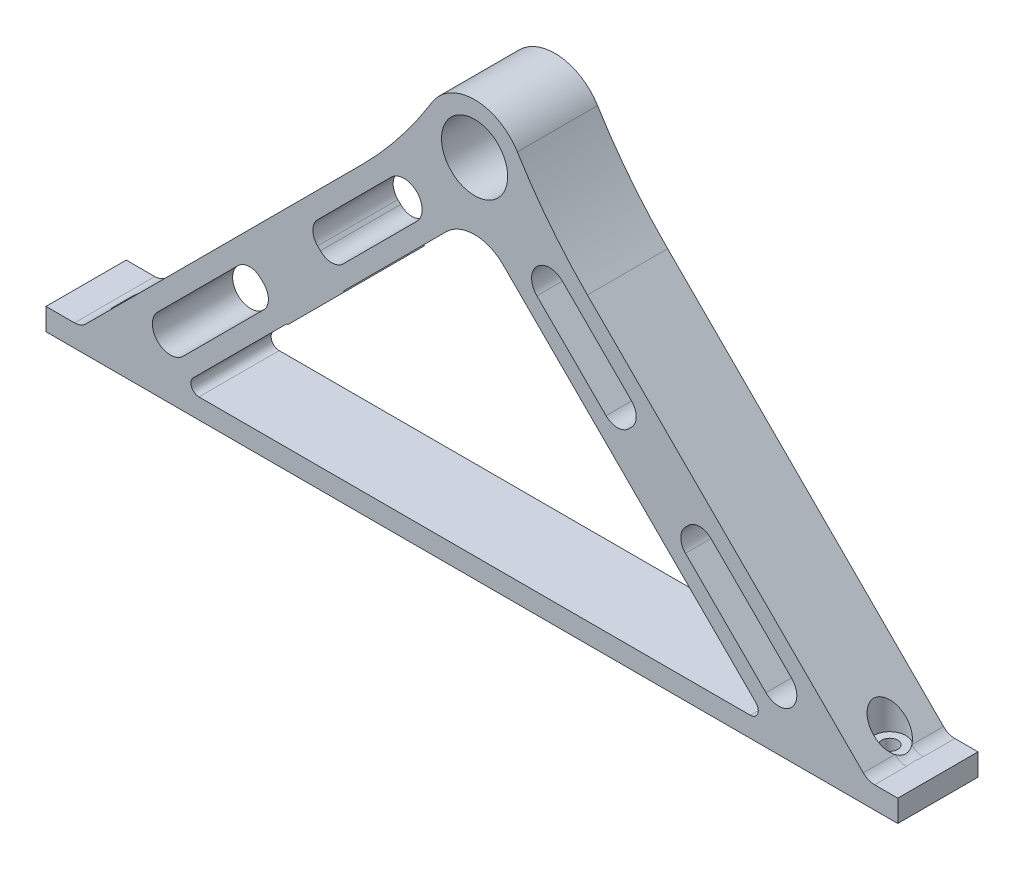
SolidWorks part; units mm, degrees
ref_plane "Ön Düzlem" through (0, 0, 0) normal (0, 0, 1) x (1, 0, 0)
ref_plane "Üst Düzlem" through (0, 0, 0) normal (0, 1, 0) x (1, 0, 0)
ref_plane "Sağ Düzlem" through (0, 0, 0) normal (1, 0, 0) x (0, 0, -1)
sketch "Çizim1" plane through (0, 0, 0) normal (0, 0, 1) x (1, 0, 0)
  line L1 (0, -12.5) -> (-73.5391, -86.0391)
  line L2 (-12.5, 0) -> (-98.0599, -85.5599)
  line L5 (0, -12.5) -> (73.5391, -86.0391)
  line L6 (12.5, 0) -> (98.0599, -85.5599)
  line L8 (-106.828, -91.0391) -> (-81.828, -91.0391)
  line L9 (105.4805, -91.0391) -> (80.4805, -91.0391)
  line L11 (-106.828, -91.0391) -> (-73.5391, -91.0391)
  line L12 (-106.828, -91.0391) -> (-106.828, -85.5599)
  line L13 (-106.828, -85.5599) -> (-98.0599, -85.5599)
  line L14 (-73.5391, -91.0391) -> (-73.5391, -86.0391)
  line L15 (105.4805, -91.0391) -> (73.5391, -91.0391)
  line L16 (105.4805, -91.0391) -> (105.4805, -85.5599)
  line L17 (105.4805, -85.5599) -> (98.0599, -85.5599)
  line L18 (73.5391, -91.0391) -> (73.5391, -86.0391)
  circle A0 centre (0, 0) radius 8.25
  arc A1 (12.5, 0) -> (-12.5, 0) centre (0, 0) ccw
  point P18 (0, 0)
  point P19 (0, 0)
  dimension "D1" = 16.5
  dimension "D2" = 25
  dimension "D3" = 5
  dimension "D4" = 5
  dimension "D5" = 104
  dimension "D6" = 104
  dimension "D7" = 121
  dimension "D8" = 121
extrude "Yükseklik-Ekstrüzyon1" add sketch "Çizim1" along normal blind 20 contours L6 A1 L2 L13 L12 L8 L11 L14 L1 L5 L18 L15 L9 L16 L17 A0 region at (-38.4398, -47.5993, 0)
sketch "Çizim2" plane through (0, -91.0391, 0) normal (0, -1, 0) x (-1, 0, 0)
  line L1 (-105.4805, -20) -> (-73.5391, -20) construction
  line L2 (-105.4805, -20) -> (-105.4805, 0) construction
  line L3 (106.828, -20) -> (106.828, 0) construction
  circle A0 centre (-93.4805, -10) radius 4
  circle A1 centre (94.828, -10) radius 4
  dimension "D2" = 8
  dimension "D5" = 8
  dimension "D1" = 10
  dimension "D3" = 12
  dimension "D4" = 12
extrude "Kes-Ekstrüzyon1" cut sketch "Çizim2" against normal blind 20 from offset 6 offset against normal yes
sketch "Çizim3" plane through (0, -85.0391, 0) normal (0, 1, 0) x (1, 0, 0)
  circle A0 centre (93.4805, -10) radius 2
  circle A1 centre (-94.828, -10) radius 2
  dimension "D1" = 4
  dimension "D2" = 4
extrude "Kes-Ekstrüzyon2" cut sketch "Çizim3" against normal blind 20
fillet "Radyus2" radius 120 2 edges at (-12.5, 0, 10) (12.5, 0, 10)
fillet "Radyus4" radius 10 1 edges at (0, -12.5, 10)
sketch "Çizim4" plane through (0, 0, 0) normal (0, 0, -1) x (-1, 0, 0)
  line L0 (-75.8112, -76.0391) -> (-18.7089, -18.9368) construction
  line L1 (-78.9932, -72.8571) -> (-21.8909, -15.7548)
  line L2 (-72.6292, -79.2211) -> (-15.5269, -22.1188)
  line L3 (17.5832, -17.8111) -> (75.8112, -76.0391) construction
  line L4 (20.7651, -14.6291) -> (78.9932, -72.8571)
  line L5 (14.4012, -20.9931) -> (72.6292, -79.2211)
  line L7 (-105.4805, -91.0391) -> (-73.5391, -91.0391) construction
  line L8 (-28.1224, -15.6224) -> (-98.0599, -85.5599) construction
  line L14 (106.828, -91.0391) -> (73.5391, -91.0391) construction
  line L15 (28.1224, -15.6224) -> (98.0599, -85.5599) construction
  arc A0 (-78.9932, -72.8571) -> (-72.6292, -79.2211) centre (-75.8112, -76.0391) ccw
  arc A1 (-15.5269, -22.1188) -> (-21.8909, -15.7548) centre (-18.7089, -18.9368) ccw
  arc A2 (20.7651, -14.6291) -> (14.4012, -20.9931) centre (17.5832, -17.8111) ccw
  arc A3 (72.6292, -79.2211) -> (78.9932, -72.8571) centre (75.8112, -76.0391) ccw
  point P2 (-47.26, -47.488)
  point P7 (46.6972, -46.9251)
  dimension "D4" = 4.5
  dimension "D5" = 4.5
  dimension "D1" = 15
  dimension "D2" = 9
  dimension "D3" = 9
  dimension "D6" = 15
  dimension "D7" = 9
  dimension "D8" = 9
extrude "Kes-Ekstrüzyon3" cut sketch "Çizim4" against normal blind 20
sketch "Çizim5" plane through (0, 0, 0) normal (0, 0, -1) x (-1, 0, 0)
  line L0 (-59.283, -46.783) -> (-45.1409, -32.6409)
  line L1 (-59.283, -46.783) -> (-47.002, -59.064)
  line L2 (-45.1409, -32.6409) -> (-32.8599, -44.9219)
  line L3 (-47.002, -59.064) -> (-32.8599, -44.9219)
  line L4 (-28.1224, -15.6224) -> (-98.0599, -85.5599) construction
  line L5 (45.1409, -32.6409) -> (59.283, -46.783)
  line L6 (45.1409, -32.6409) -> (32.4802, -45.3015)
  line L7 (59.283, -46.783) -> (46.6224, -59.4436)
  line L8 (32.4802, -45.3015) -> (46.6224, -59.4436)
  line L9 (28.1224, -15.6224) -> (98.0599, -85.5599) construction
  dimension "D1" = 55
  dimension "D2" = 20
  dimension "D3" = 55
  dimension "D4" = 20
extrude "Yükseklik-Ekstrüzyon2" add sketch "Çizim5" against normal up to surface (20 mm away) up to face at (47.26, -47.488, 20)
fillet "Radyus5" radius 4 8 edges at (56.101, -49.965, 10) (49.7371, -56.329, 10) (41.9589, -35.8229, 10) (35.5949, -42.1868, 10) (-49.7371, -56.329, 10) (-56.101, -49.965, 10) (-35.5949, -42.1868, 10) (-41.9589, -35.8229, 10)
sketch "Çizim6" plane through (0, 0, 0) normal (0, 0, -1) x (-1, 0, 0)
sketch "Çizim7" plane through (0, 0, 0) normal (0, 0, -1) x (-1, 0, 0)
  line L1 (-73.5391, -86.0391) -> (73.5391, -86.0391)
  line L2 (-73.5391, -86.0391) -> (-73.5391, -91.0391)
  line L3 (-73.5391, -91.0391) -> (73.5391, -91.0391)
  line L4 (73.5391, -86.0391) -> (73.5391, -91.0391)
extrude "Yükseklik-Ekstrüzyon3" add sketch "Çizim7" against normal up to surface (20 mm away) up to face at (-61.8276, -62.0556, 20)
sketch "Çizim8" plane through (0, -91.0391, 0) normal (0, -1, 0) x (-1, 0, 0)
fillet "Radyus7" radius 4 2 edges at (98.0599, -85.5599, 10) (-98.0599, -85.5599, 10)
fillet "Radyus8" radius 2 2 edges at (73.5391, -86.0391, 10) (-73.5391, -86.0391, 10)
